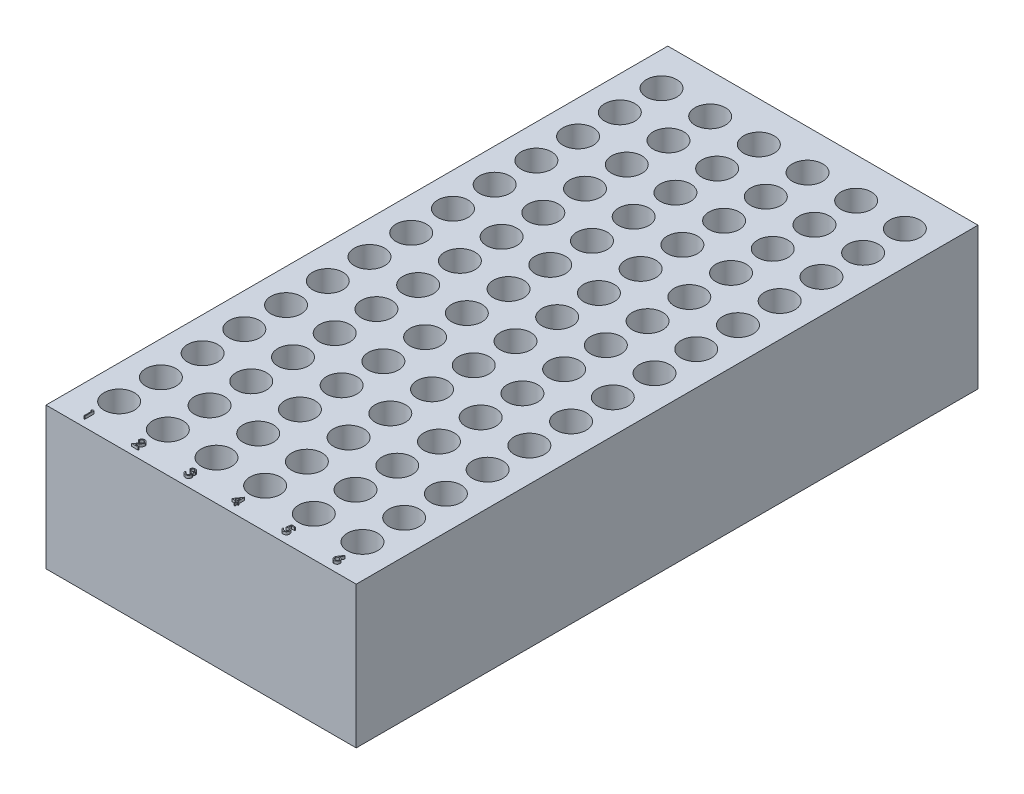
SolidWorks part; units mm, degrees
ref_plane "Front Plane" through (0, 0, 0) normal (0, 0, 1) x (1, 0, 0)
ref_plane "Top Plane" through (0, 0, 0) normal (0, 1, 0) x (1, 0, 0)
ref_plane "Right Plane" through (0, 0, 0) normal (1, 0, 0) x (0, 0, -1)
sketch "Sketch1" plane through (0, 0, 0) normal (0, 1, 0) x (1, 0, 0)
  line L0 (-45.1964, 100.75) -> (-57.625, 100.75) construction
  line L1 (57.625, -115.5) -> (-57.625, -115.5)
  line L2 (57.625, -115.5) -> (57.625, 115.5)
  line L3 (57.625, 115.5) -> (-57.625, 115.5)
  line L4 (-57.625, -115.5) -> (-57.625, 115.5)
  line L5 (57.625, -115.5) -> (-57.625, 115.5) construction
  line L6 (57.625, 115.5) -> (-57.625, -115.5) construction
  line L7 (45.1964, 100.75) -> (57.625, 100.75) construction
  line L8 (-45.1964, 100.75) -> (-45.1964, 115.5) construction
  line L9 (-27.1179, 100.75) -> (-39.5464, 100.75) construction
  line L10 (-45.1964, -100.75) -> (-57.625, -100.75) construction
  line L11 (-45.1964, -100.75) -> (-45.1964, -115.5) construction
  circle A0 centre (-45.1964, 100.75) radius 5.65
  circle A1 centre (-27.1179, 100.75) radius 5.65
  circle A2 centre (-9.0393, 100.75) radius 5.65
  circle A3 centre (9.0393, 100.75) radius 5.65
  circle A4 centre (27.1179, 100.75) radius 5.65
  circle A5 centre (45.1964, 100.75) radius 5.65
  circle A6 centre (-45.1964, 85.25) radius 5.65
  circle A7 centre (-27.1179, 85.25) radius 5.65
  circle A8 centre (-9.0393, 85.25) radius 5.65
  circle A9 centre (9.0393, 85.25) radius 5.65
  circle A10 centre (27.1179, 85.25) radius 5.65
  circle A11 centre (45.1964, 85.25) radius 5.65
  circle A12 centre (-45.1964, 69.75) radius 5.65
  circle A13 centre (-27.1179, 69.75) radius 5.65
  circle A14 centre (-9.0393, 69.75) radius 5.65
  circle A15 centre (9.0393, 69.75) radius 5.65
  circle A16 centre (27.1179, 69.75) radius 5.65
  circle A17 centre (45.1964, 69.75) radius 5.65
  circle A18 centre (-45.1964, 54.25) radius 5.65
  circle A19 centre (-27.1179, 54.25) radius 5.65
  circle A20 centre (-9.0393, 54.25) radius 5.65
  circle A21 centre (9.0393, 54.25) radius 5.65
  circle A22 centre (27.1179, 54.25) radius 5.65
  circle A23 centre (45.1964, 54.25) radius 5.65
  circle A24 centre (-45.1964, 38.75) radius 5.65
  circle A25 centre (-27.1179, 38.75) radius 5.65
  circle A26 centre (-9.0393, 38.75) radius 5.65
  circle A27 centre (9.0393, 38.75) radius 5.65
  circle A28 centre (27.1179, 38.75) radius 5.65
  circle A29 centre (45.1964, 38.75) radius 5.65
  circle A30 centre (-45.1964, 23.25) radius 5.65
  circle A31 centre (-27.1179, 23.25) radius 5.65
  circle A32 centre (-9.0393, 23.25) radius 5.65
  circle A33 centre (9.0393, 23.25) radius 5.65
  circle A34 centre (27.1179, 23.25) radius 5.65
  circle A35 centre (45.1964, 23.25) radius 5.65
  circle A36 centre (-45.1964, 7.75) radius 5.65
  circle A37 centre (-27.1179, 7.75) radius 5.65
  circle A38 centre (-9.0393, 7.75) radius 5.65
  circle A39 centre (9.0393, 7.75) radius 5.65
  circle A40 centre (27.1179, 7.75) radius 5.65
  circle A41 centre (45.1964, 7.75) radius 5.65
  circle A42 centre (-45.1964, -7.75) radius 5.65
  circle A43 centre (-27.1179, -7.75) radius 5.65
  circle A44 centre (-9.0393, -7.75) radius 5.65
  circle A45 centre (9.0393, -7.75) radius 5.65
  circle A46 centre (27.1179, -7.75) radius 5.65
  circle A47 centre (45.1964, -7.75) radius 5.65
  circle A48 centre (-45.1964, -23.25) radius 5.65
  circle A49 centre (-27.1179, -23.25) radius 5.65
  circle A50 centre (-9.0393, -23.25) radius 5.65
  circle A51 centre (9.0393, -23.25) radius 5.65
  circle A52 centre (27.1179, -23.25) radius 5.65
  circle A53 centre (45.1964, -23.25) radius 5.65
  circle A54 centre (-45.1964, -38.75) radius 5.65
  circle A55 centre (-27.1179, -38.75) radius 5.65
  circle A56 centre (-9.0393, -38.75) radius 5.65
  circle A57 centre (9.0393, -38.75) radius 5.65
  circle A58 centre (27.1179, -38.75) radius 5.65
  circle A59 centre (45.1964, -38.75) radius 5.65
  circle A60 centre (-45.1964, -54.25) radius 5.65
  circle A61 centre (-27.1179, -54.25) radius 5.65
  circle A62 centre (-9.0393, -54.25) radius 5.65
  circle A63 centre (9.0393, -54.25) radius 5.65
  circle A64 centre (27.1179, -54.25) radius 5.65
  circle A65 centre (45.1964, -54.25) radius 5.65
  circle A66 centre (-45.1964, -69.75) radius 5.65
  circle A67 centre (-27.1179, -69.75) radius 5.65
  circle A68 centre (-9.0393, -69.75) radius 5.65
  circle A69 centre (9.0393, -69.75) radius 5.65
  circle A70 centre (27.1179, -69.75) radius 5.65
  circle A71 centre (45.1964, -69.75) radius 5.65
  circle A72 centre (-45.1964, -85.25) radius 5.65
  circle A73 centre (-27.1179, -85.25) radius 5.65
  circle A74 centre (-9.0393, -85.25) radius 5.65
  circle A75 centre (9.0393, -85.25) radius 5.65
  circle A76 centre (27.1179, -85.25) radius 5.65
  circle A77 centre (45.1964, -85.25) radius 5.65
  circle A78 centre (-45.1964, -100.75) radius 5.65
  circle A79 centre (-27.1179, -100.75) radius 5.65
  circle A80 centre (-9.0393, -100.75) radius 5.65
  circle A81 centre (9.0393, -100.75) radius 5.65
  circle A82 centre (27.1179, -100.75) radius 5.65
  circle A83 centre (45.1964, -100.75) radius 5.65
  point P0 (0, 0)
  dimension "D1" = 11.3
  dimension "D3" = 18.0786
  dimension "D7" = 231
  dimension "D8" = 15.5
  dimension "D9" = 115.25
  dimension "D2" = 6
  dimension "D6" = 14
extrude "Boss-Extrude1" add sketch "Sketch1" along normal blind 21.7
sketch "Sketch2" plane through (0, 0, 0) normal (0, -1, 0) x (1, 0, 0)
  line L1 (57.625, -115.5) -> (-57.625, -115.5)
  line L2 (57.625, -115.5) -> (57.625, 115.5)
  line L3 (57.625, 115.5) -> (-57.625, 115.5)
  line L4 (-57.625, -115.5) -> (-57.625, 115.5)
  line L5 (57.625, -115.5) -> (-57.625, 115.5) construction
  line L6 (57.625, 115.5) -> (-57.625, -115.5) construction
  point P0 (0, 0)
extrude "Boss-Extrude2" add sketch "Sketch2" along normal blind 31
sketch "Sketch6" plane through (0, 0, 0) normal (0, 1, 0) x (1, 0, 0)
  circle A1 centre (-45.1964, 100.75) radius 4.225
  circle A2 centre (-27.1164, 100.75) radius 4.225
  circle A3 centre (-9.0364, 100.75) radius 4.225
  circle A4 centre (9.0436, 100.75) radius 4.225
  circle A5 centre (27.1236, 100.75) radius 4.225
  circle A6 centre (45.2036, 100.75) radius 4.225
  circle A7 centre (-45.1964, 85.25) radius 4.225
  circle A8 centre (-27.1164, 85.25) radius 4.225
  circle A9 centre (-9.0364, 85.25) radius 4.225
  circle A10 centre (9.0436, 85.25) radius 4.225
  circle A11 centre (27.1236, 85.25) radius 4.225
  circle A12 centre (45.2036, 85.25) radius 4.225
  circle A13 centre (-45.1964, 69.75) radius 4.225
  circle A14 centre (-27.1164, 69.75) radius 4.225
  circle A15 centre (-9.0364, 69.75) radius 4.225
  circle A16 centre (9.0436, 69.75) radius 4.225
  circle A17 centre (27.1236, 69.75) radius 4.225
  circle A18 centre (45.2036, 69.75) radius 4.225
  circle A19 centre (-45.1964, 54.25) radius 4.225
  circle A20 centre (-27.1164, 54.25) radius 4.225
  circle A21 centre (-9.0364, 54.25) radius 4.225
  circle A22 centre (9.0436, 54.25) radius 4.225
  circle A23 centre (27.1236, 54.25) radius 4.225
  circle A24 centre (45.2036, 54.25) radius 4.225
  circle A25 centre (-45.1964, 38.75) radius 4.225
  circle A26 centre (-27.1164, 38.75) radius 4.225
  circle A27 centre (-9.0364, 38.75) radius 4.225
  circle A28 centre (9.0436, 38.75) radius 4.225
  circle A29 centre (27.1236, 38.75) radius 4.225
  circle A30 centre (45.2036, 38.75) radius 4.225
  circle A31 centre (-45.1964, 23.25) radius 4.225
  circle A32 centre (-27.1164, 23.25) radius 4.225
  circle A33 centre (-9.0364, 23.25) radius 4.225
  circle A34 centre (9.0436, 23.25) radius 4.225
  circle A35 centre (27.1236, 23.25) radius 4.225
  circle A36 centre (45.2036, 23.25) radius 4.225
  circle A37 centre (-45.1964, 7.75) radius 4.225
  circle A38 centre (-27.1164, 7.75) radius 4.225
  circle A39 centre (-9.0364, 7.75) radius 4.225
  circle A40 centre (9.0436, 7.75) radius 4.225
  circle A41 centre (27.1236, 7.75) radius 4.225
  circle A42 centre (45.2036, 7.75) radius 4.225
  circle A43 centre (-45.1964, -7.75) radius 4.225
  circle A44 centre (-27.1164, -7.75) radius 4.225
  circle A45 centre (-9.0364, -7.75) radius 4.225
  circle A46 centre (9.0436, -7.75) radius 4.225
  circle A47 centre (27.1236, -7.75) radius 4.225
  circle A48 centre (45.2036, -7.75) radius 4.225
  circle A49 centre (-45.1964, -23.25) radius 4.225
  circle A50 centre (-27.1164, -23.25) radius 4.225
  circle A51 centre (-9.0364, -23.25) radius 4.225
  circle A52 centre (9.0436, -23.25) radius 4.225
  circle A53 centre (27.1236, -23.25) radius 4.225
  circle A54 centre (45.2036, -23.25) radius 4.225
  circle A55 centre (-45.1964, -38.75) radius 4.225
  circle A56 centre (-27.1164, -38.75) radius 4.225
  circle A57 centre (-9.0364, -38.75) radius 4.225
  circle A58 centre (9.0436, -38.75) radius 4.225
  circle A59 centre (27.1236, -38.75) radius 4.225
  circle A60 centre (45.2036, -38.75) radius 4.225
  circle A61 centre (-45.1964, -54.25) radius 4.225
  circle A62 centre (-27.1164, -54.25) radius 4.225
  circle A63 centre (-9.0364, -54.25) radius 4.225
  circle A64 centre (9.0436, -54.25) radius 4.225
  circle A65 centre (27.1236, -54.25) radius 4.225
  circle A66 centre (45.2036, -54.25) radius 4.225
  circle A67 centre (-45.1964, -69.75) radius 4.225
  circle A68 centre (-27.1164, -69.75) radius 4.225
  circle A69 centre (-9.0364, -69.75) radius 4.225
  circle A70 centre (9.0436, -69.75) radius 4.225
  circle A71 centre (27.1236, -69.75) radius 4.225
  circle A72 centre (45.2036, -69.75) radius 4.225
  circle A73 centre (-45.1964, -85.25) radius 4.225
  circle A74 centre (-27.1164, -85.25) radius 4.225
  circle A75 centre (-9.0364, -85.25) radius 4.225
  circle A76 centre (9.0436, -85.25) radius 4.225
  circle A77 centre (27.1236, -85.25) radius 4.225
  circle A78 centre (45.2036, -85.25) radius 4.225
  circle A79 centre (-45.1964, -100.75) radius 4.225
  circle A80 centre (-27.1164, -100.75) radius 4.225
  circle A81 centre (-9.0364, -100.75) radius 4.225
  circle A82 centre (9.0436, -100.75) radius 4.225
  circle A83 centre (27.1236, -100.75) radius 4.225
  circle A84 centre (45.2036, -100.75) radius 4.225
  circle A94 centre (-45.1964, 100.75) radius 5.65 construction
  dimension "D5" = 8.45
  dimension "D3" = 15.5
  dimension "D4" = 18.08
  dimension "D1" = 6
  dimension "D2" = 14
extrude "Cut-Extrude1" cut sketch "Sketch6" against normal blind 30
shell "Shell11" thickness 0.5 removed face at (0, -31, 0)
sketch "Sketch5" plane through (0, 21.7, 0) normal (0, 1, 0) x (1, 0, 0)
  text T0 "1            2            3           4            5            6"
extrude "Boss-Extrude5" add sketch "Sketch5" along normal blind 1
